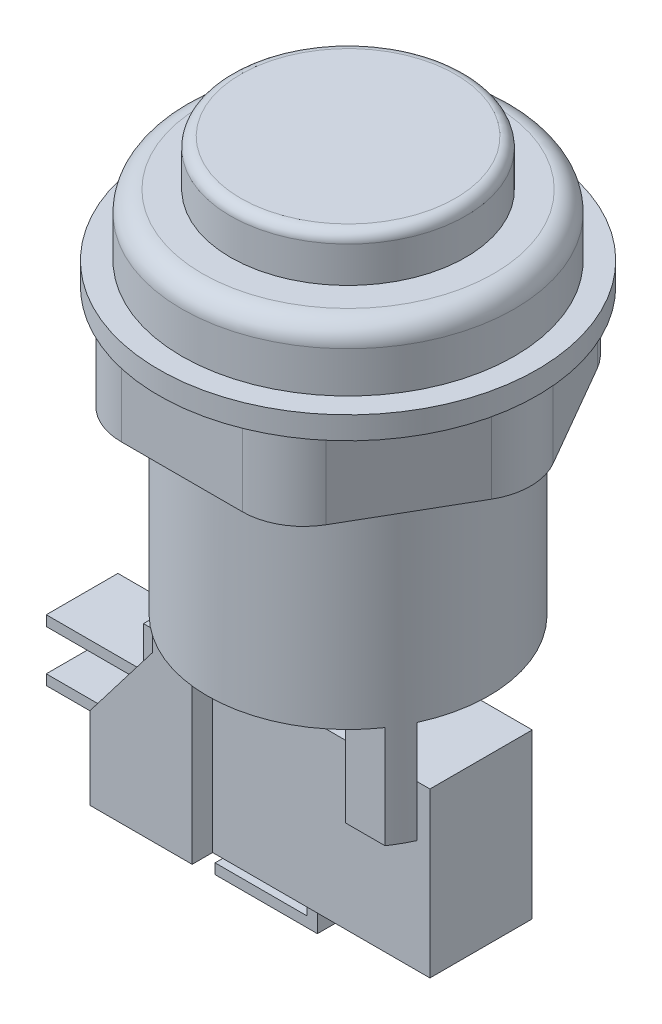
SolidWorks part; units mm, degrees
ref_plane "Alzado" through (0, 0, 0) normal (0, 0, 1) x (1, 0, 0)
ref_plane "Planta" through (0, 0, 0) normal (0, 1, 0) x (1, 0, 0)
ref_plane "Vista lateral" through (0, 0, 0) normal (1, 0, 0) x (0, 0, -1)
sketch "Croquis1" plane through (0, 0, 0) normal (0, 1, 0) x (1, 0, 0)
  circle A0 centre (0, 0) radius 11.5
  dimension "D1" = 23
extrude "Saliente-Extruir1" add sketch "Croquis1" along normal blind 4.5
fillet "Redondeo1" radius 1 1 edges at (0, 4.5, 11.5)
sketch "Croquis2" plane through (0, 0, 0) normal (0, -1, 0) x (1, 0, 0)
  circle A0 centre (0, 0) radius 16.25
  dimension "D1" = 32.5
extrude "Saliente-Extruir2" add sketch "Croquis2" along normal blind 6
fillet "Redondeo2" radius 2 1 edges at (0, 0, -16.25)
sketch "Croquis3" plane through (0, -6, 0) normal (0, -1, 0) x (1, 0, 0)
  circle A0 centre (0, 0) radius 13.75
  dimension "D1" = 27.5
extrude "Saliente-Extruir3" add sketch "Croquis3" along normal blind 30
sketch "Croquis5" plane through (0, -6, 0) normal (0, -1, 0) x (1, 0, 0)
  circle A0 centre (0, 0) radius 18.5
  dimension "D1" = 37
extrude "Saliente-Extruir4" add sketch "Croquis5" along normal blind 2.2
sketch "Croquis6" plane through (0, -8.2, 0) normal (0, -1, 0) x (1, 0, 0)
  line L1 (18.7639, 0) -> (9.3819, 16.25)
  line L2 (9.3819, 16.25) -> (-9.3819, 16.25)
  line L3 (-9.3819, 16.25) -> (-18.7639, 0)
  line L4 (-18.7639, 0) -> (-9.3819, -16.25)
  line L5 (-9.3819, -16.25) -> (9.3819, -16.25)
  line L6 (9.3819, -16.25) -> (18.7639, 0)
  circle A0 centre (0, 0) radius 16.25 construction
  dimension "D1" = 32.5
extrude "Saliente-Extruir5" add sketch "Croquis6" along normal blind 8
fillet "Redondeo3" radius 6 6 edges at (-9.3819, -12.2, 16.25) (-18.7639, -12.2, 0) (-9.3819, -12.2, -16.25) (9.3819, -12.2, -16.25) (18.7639, -12.2, 0) (9.3819, -12.2, 16.25)
sketch "Croquis7" plane through (0, -36, 0) normal (0, -1, 0) x (1, 0, 0)
  line L0 (-11.3578, 7.75) -> (11.3578, 7.75) construction
  line L1 (0, 13.75) -> (0, -13.2129) construction
  line L2 (-7.49, 5.75) -> (-12.49, 5.75)
  line L3 (-7.49, 5.75) -> (-7.49, 7.75)
  line L4 (-7.49, 7.75) -> (-11.3578, 7.75)
  line L6 (7.49, 7.75) -> (11.3578, 7.75)
  line L7 (7.49, 7.75) -> (7.49, 5.75)
  line L8 (7.49, 5.75) -> (12.49, 5.75)
  line L10 (-8.4423, 5.75) -> (11.3578, 5.75) construction
  line L11 (-8.4423, 5.75) -> (-8.4423, -4.25) construction
  line L12 (-8.4423, -4.25) -> (11.3578, -4.25) construction
  line L13 (11.3578, 5.75) -> (11.3578, -4.25) construction
  line L15 (-5, -4.25) -> (5, -4.25)
  line L16 (-5, -4.25) -> (-5, -6.25)
  line L17 (-5, -6.25) -> (5, -6.25)
  line L18 (5, -4.25) -> (5, -6.25)
  line L19 (-5, -4.25) -> (5, -6.25) construction
  line L20 (-5, -6.25) -> (5, -4.25) construction
  circle A0 centre (0, 0) radius 13.75 construction
  arc A1 (12.49, 5.75) -> (11.3578, 7.75) centre (0, 0) ccw
  arc A2 (-11.3578, 7.75) -> (-12.49, 5.75) centre (0, 0) ccw
  point P19 (0, -5.25)
  dimension "D1" = 6
  dimension "D2" = 5
  dimension "D3" = 5
  dimension "D4" = 2
  dimension "D5" = 2
  dimension "D6" = 10
  dimension "D7" = 2
  dimension "D8" = 10
extrude "Saliente-Extruir6" add sketch "Croquis7" along normal blind 10
sketch "Croquis8" plane through (0, -46, 0) normal (0, -1, 0) x (1, 0, 0)
  line L0 (-12.49, 5.75) -> (-7.49, 5.75) construction
  line L1 (-7.49, 7.75) -> (-17.49, 7.75)
  line L2 (-7.49, 7.75) -> (-7.49, 5.75)
  line L3 (-7.49, 5.75) -> (-17.49, 5.75)
  line L4 (-17.49, 7.75) -> (-17.49, 5.75)
  dimension "D1" = 10
extrude "Saliente-Extruir7" add sketch "Croquis8" along normal blind 11
sketch "Croquis9" plane through (0, 0, 7.75) normal (0, 0, 1) x (1, 0, 0)
  line L0 (-17.49, -49) -> (-7.49, -49) construction
  line L1 (-17.49, -57) -> (-17.49, -46) construction
  line L2 (-7.49, -57) -> (-7.49, -36) construction
  line L3 (-7.49, -57) -> (-17.49, -57) construction
  line L4 (-17.49, -49) -> (-11.3578, -41)
  line L5 (-11.3578, -46) -> (-11.3578, -36) construction
  line L6 (-11.3578, -41) -> (-11.3578, -49)
  line L7 (-11.3578, -49) -> (-17.49, -49)
  dimension "D1" = 8
  dimension "D2" = 8
extrude "Saliente-Extruir8" add sketch "Croquis9" against normal up to surface (2 mm away) up to face at (-12.49, -46.3333, 5.75)
ref_plane "Plano1" through (-7.49, -57, 7.75) normal (0, 1, 0) x (1, 0, 0)
sketch "Croquis11" plane through (0, 0, 7.75) normal (0, 0, 1) x (1, 0, 0)
  line L0 (-15.1904, -46) -> (-17.49, -49)
  line L1 (-17.49, -57) -> (-17.49, -46) construction
  line L2 (-11.3578, -41) -> (-15.1904, -46) construction
  line L3 (-17.49, -46) -> (-17.49, -49)
  line L4 (-17.49, -46) -> (-15.1904, -46)
extrude "Cortar-Extruir1" cut sketch "Croquis11" against normal through all
ref_plane "Plano2" through (0, -41, 0) normal (0, -1, 0) x (-1, 0, 0)
sketch "Croquis12" plane through (0, -41, 0) normal (0, -1, 0) x (-1, 0, 0)
  line L6 (-5, 4.25) -> (5, 4.25) construction
  line L7 (-13.75, 4.25) -> (14.25, 4.25)
  line L8 (-13.75, 4.25) -> (-13.75, -5.75)
  line L9 (-13.75, -5.75) -> (14.25, -5.75)
  line L10 (14.25, 4.25) -> (14.25, -5.75)
  line L11 (-7.49, -5.75) -> (-12.49, -5.75) construction
  arc A2 (12.49, -5.75) -> (-12.49, -5.75) centre (0, 0) ccw construction
  dimension "D1" = 28
extrude "Saliente-Extruir9" add sketch "Croquis12" along normal blind 16
sketch "Croquis13" plane through (0, -57, 0) normal (0, -1, 0) x (1, 0, 0)
  line L1 (-0.5, 3.5) -> (0.5, 3.5)
  line L2 (-0.5, 3.5) -> (-0.5, -3.5)
  line L3 (-0.5, -3.5) -> (0.5, -3.5)
  line L4 (0.5, 3.5) -> (0.5, -3.5)
  line L5 (-0.5, 3.5) -> (0.5, -3.5) construction
  line L6 (-0.5, -3.5) -> (0.5, 3.5) construction
  point P0 (0, 0)
  dimension "D1" = 1
  dimension "D2" = 7
extrude "Saliente-Extruir10" add sketch "Croquis13" along normal blind 4
sketch "Croquis14" plane through (-0.5, 0, 0) normal (-1, 0, 0) x (0, 0, 1)
  line L0 (3.5, -61) -> (3.5, -57) construction
  line L1 (-3.5, -61) -> (3.5, -61)
  line L2 (-3.5, -61) -> (-3.5, -60)
  line L3 (-3.5, -60) -> (3.5, -60)
  line L4 (3.5, -61) -> (3.5, -60)
  dimension "D1" = 1
extrude "Saliente-Extruir11" add sketch "Croquis14" along normal blind 9
sketch "Croquis15" plane through (-14.25, 0, 0) normal (-1, 0, 0) x (0, 0, 1)
  line L0 (0.75, -57) -> (0.75, -41) construction
  line L1 (5.75, -57) -> (-4.25, -57) construction
  line L2 (-15.125, -41) -> (15.125, -41) construction
  line L3 (3.5, -57) -> (-3.5, -57) construction
  line L4 (-2.75, -46.5) -> (4.25, -46.5)
  line L5 (-2.75, -46.5) -> (-2.75, -47.5)
  line L6 (-2.75, -47.5) -> (4.25, -47.5)
  line L7 (4.25, -46.5) -> (4.25, -47.5)
  line L8 (-2.75, -46.5) -> (4.25, -47.5) construction
  line L9 (-2.75, -47.5) -> (4.25, -46.5) construction
  line L10 (-2.75, -51.5) -> (4.25, -51.5)
  line L11 (-2.75, -51.5) -> (-2.75, -52.5)
  line L12 (-2.75, -52.5) -> (4.25, -52.5)
  line L13 (4.25, -51.5) -> (4.25, -52.5)
  line L14 (-2.75, -51.5) -> (4.25, -52.5) construction
  line L15 (-2.75, -52.5) -> (4.25, -51.5) construction
  point P6 (0.75, -47)
  point P11 (0.75, -52)
  dimension "D1" = 7
  dimension "D2" = 7
  dimension "D3" = 4.5
  dimension "D4" = 4
  dimension "D5" = 1
  dimension "D6" = 1
extrude "Saliente-Extruir12" add sketch "Croquis15" along normal blind 11
